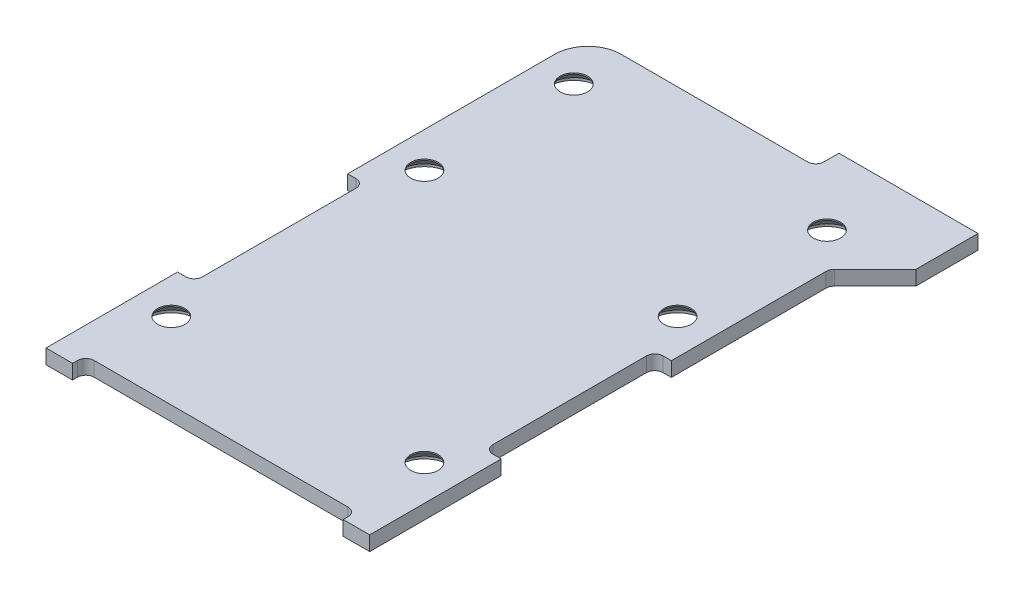
SolidWorks part; units mm, degrees
ref_plane "Front Plane" through (0, 0, 0) normal (0, 0, 1) x (1, 0, 0)
ref_plane "Top Plane" through (0, 0, 0) normal (0, 1, 0) x (1, 0, 0)
ref_plane "Right Plane" through (0, 0, 0) normal (1, 0, 0) x (0, 0, -1)
sketch "Sketch1" plane through (0, 0, 0) normal (0, 1, 0) x (1, 0, 0)
  line L1 (-18, 31.1) -> (18, 31.1)
  line L2 (-18, 31.1) -> (-18, -31.1)
  line L3 (-18, -31.1) -> (18, -31.1)
  line L4 (18, 31.1) -> (18, -31.1)
  line L5 (-18, 31.1) -> (18, -31.1) construction
  line L6 (-18, -31.1) -> (18, 31.1) construction
  point P0 (0, 0)
  dimension "D1" = 36
  dimension "D2" = 62.2
extrude "Base shape" add sketch "Sketch1" along normal blind 1.75
sketch "Sketch2" plane through (0, 1.75, 0) normal (0, 1, 0) x (1, 0, 0)
  line L0 (0, 31.1) -> (0, -31.1) construction
  line L1 (18, 31.1) -> (-18, 31.1) construction
  line L2 (-18, -31.1) -> (18, -31.1) construction
  line L4 (-18, 2.15) -> (-17.5, 2.15)
  line L5 (-18, 2.15) -> (-18, -18.35)
  line L6 (-18, -18.35) -> (-17.5, -18.35)
  line L7 (-17.5, 2.15) -> (-17.5, -18.35)
  line L8 (-17.5, -8.1) -> (-18, -8.1) construction
  line L9 (-15.25, -31.1) -> (-15.25, 31.1) construction
  line L11 (-18, -8.1) -> (18, -8.1) construction
  line L13 (15.25, 7.15) -> (15.25, -8.1) construction
  line L14 (15.25, 7.15) -> (0, 7.15) construction
  line L15 (18, -18.35) -> (17.5, -18.35)
  line L16 (17.5, 2.15) -> (17.5, -18.35)
  line L17 (18, 2.15) -> (17.5, 2.15)
  line L18 (18, 2.15) -> (18, -18.35)
  line L19 (18, -31.1) -> (18, 31.1) construction
  line L20 (-18, -31.1) -> (18, -31.1)
  line L21 (-18, -31.1) -> (-18, 14.9)
  line L22 (-18, 14.9) -> (18, 14.9)
  line L23 (18, -31.1) -> (18, 14.9)
  circle A0 centre (15.25, 7.15) radius 1.65
  circle A1 centre (15.25, -23.35) radius 1.65
  circle A2 centre (-15.25, 7.15) radius 1.65
  circle A3 centre (-15.25, -23.35) radius 1.65
  circle A4 centre (-15.25, 25.15) radius 1.65
  circle A5 centre (15.25, 25.15) radius 1.65
  line M13 (18, -31.1) -> (18, 31.1)
  line M15 (-18, 31.1) -> (-18, -31.1)
  dimension "D4" = 3.3
  dimension "D1" = 20.5
  dimension "D2" = 46
  dimension "D3" = 35
  dimension "D5" = 30.5
  dimension "D6" = 18
extrude "Cutouts" cut sketch "Sketch2" against normal up to next contours A2 | A0 | L17 L16 L15 M13 | L7 L4 L6 M15 | A3 | A1 | A4 | A5 region at (-17.75, 1.75, 8.1) region at (17.75, 1.75, 8.1) region at (15.25, 1.75, -7.15) region at (15.25, 1.75, 23.35) region at (-15.25, 1.75, -7.15) region at (-15.25, 1.75, 23.35)
sketch "Sketch3" plane through (0, 0, 0) normal (0, -1, 0) x (1, 0, 0)
  line L0 (18, -16.625) -> (19.5, -16.625) construction
  line L1 (19.5, 32.6) -> (-19.5, 32.6)
  line L2 (19.5, 32.6) -> (19.5, -32.6)
  line L3 (19.5, -32.6) -> (-19.5, -32.6)
  line L4 (-19.5, 32.6) -> (-19.5, -32.6)
  line L5 (19.5, 32.6) -> (-19.5, -32.6) construction
  line L6 (19.5, -32.6) -> (-19.5, 32.6) construction
  line L7 (0, -31.1) -> (0, -32.6) construction
  line L8 (-19.5, -31.1) -> (19.5, -31.1)
  line L9 (-19.5, -2.15) -> (19.5, -2.15)
  line L10 (-19.5, 18.35) -> (19.5, 18.35)
  line L11 (-19.5, 31.1) -> (19.5, 31.1)
  line L12 (-18, 18.35) -> (-17.5, 18.35)
  line L13 (-18, 31.1) -> (-18, 18.35)
  line L14 (18, 31.1) -> (-18, 31.1)
  line L15 (18, 18.35) -> (18, 31.1)
  line L16 (17.5, 18.35) -> (18, 18.35)
  line L17 (17.5, -2.15) -> (17.5, 18.35)
  line L18 (18, -2.15) -> (17.5, -2.15)
  line L19 (18, -31.1) -> (18, -2.15)
  line L20 (-18, -31.1) -> (18, -31.1)
  line L21 (-18, -2.15) -> (-18, -31.1)
  line L22 (-17.5, -2.15) -> (-18, -2.15)
  line L23 (-17.5, 18.35) -> (-17.5, -2.15)
  line L24 (-18, 18.35) -> (-17.5, 18.35)
  line L25 (-18, 31.1) -> (-18, 18.35)
  line L26 (18, 31.1) -> (-18, 31.1)
  line L27 (18, 18.35) -> (18, 31.1)
  line L28 (17.5, 18.35) -> (18, 18.35)
  line L29 (17.5, -2.15) -> (17.5, 18.35)
  line L30 (18, -2.15) -> (17.5, -2.15)
  line L31 (18, -31.1) -> (18, -2.15)
  line L32 (-18, -31.1) -> (18, -31.1)
  line L33 (-18, -2.15) -> (-18, -31.1)
  line L34 (-17.5, -2.15) -> (-18, -2.15)
  line L35 (-17.5, 18.35) -> (-17.5, -2.15)
  line L37 (24.7, -26.4) -> (24.7, -33.9) construction
  line L38 (7.95, -33.9) -> (24.7, -33.9) construction
  line L39 (7.95, -33.9) -> (7.95, -14.9) construction
  line L40 (24.7, -26.4) -> (19.5, -21.2) construction
  line L41 (24.7, -26.4) -> (24.7, -33.9)
  line L42 (7.95, -33.9) -> (24.7, -33.9)
  line L43 (7.95, -33.9) -> (7.95, -14.9)
  line L44 (24.7, -26.4) -> (19.5, -21.2)
  point P2 (0, 0)
  line M15 (18, -31.1) -> (18, -2.15)
  line M16 (18, 31.1) -> (-18, 31.1)
  line M17 (-18, 31.1) -> (-18, 18.35)
  line M35 (-18, -2.15) -> (-18, -31.1)
  line M36 (18, 18.35) -> (18, 31.1)
  dimension "D2" = 1.5
  dimension "D1" = 0
extrude "Extra size" add sketch "Sketch3" against normal up to surface (1.75 mm away) contours L9 L4 L8 M35 | L9 L8 L2 M15 | L11 L4 L10 M17 | L11 L10 L2 M36 | L4 L11 L2 L1 M16 | L43 L42 L41 L2 L3 | L43 L3 L2 L8 L32 region at (0, 0, 31.85) region at (18.75, 0, 24.725) region at (-18.75, 0, 24.725) region at (18.75, 0, -16.625) region at (-18.75, 0, -16.625) region at (20.0645, 0, -29.7415) region at (13.725, 0, -31.85) up to face at (15.25, 1.75, 25)
sketch "Sketch4" plane through (0, 0, 0) normal (0, 1, 0) x (1, 0, 0)
  circle A0 centre (-15.25, 25.15) radius 3
  circle A1 centre (15.25, 25.15) radius 3
  circle A2 centre (15.25, 7.15) radius 3
  circle A3 centre (-15.25, 7.15) radius 3
  circle A4 centre (-15.25, -23.35) radius 3
  circle A5 centre (15.25, -23.35) radius 3
  dimension "D1" = 6
extrude "Screw head cut" cut sketch "Sketch4" along normal blind 0.4
chamfer "Screw chamfer" distance 1.2 angle 45 6 edges at (-15.25, 0.4, 25) (15.25, 0.4, 25) (15.25, 0.4, -5.5) (15.25, 0.4, -23.5) (-15.25, 0.4, -23.5) (-15.25, 0.4, -5.5)
fillet "Front fillets" radius 4 1 edges at (-19.5, 0.875, -31.1)
sketch "Sketch6" plane through (0, 0, 32.6) normal (0, 0, 1) x (1, 0, 0)
  line L0 (19.5, 0) -> (-19.5, 0) construction
  line L1 (19.5, 1.75) -> (16.3, 1.75)
  line L2 (19.5, 1.75) -> (19.5, 0)
  line L3 (19.5, 0) -> (16.3, 0)
  line L4 (16.3, 1.75) -> (16.3, 0)
  line L7 (-19.5, 0) -> (-16.3, 0)
  line L8 (-19.5, 0) -> (-19.5, 1.75)
  line L9 (-19.5, 1.75) -> (-16.3, 1.75)
  line L10 (-16.3, 0) -> (-16.3, 1.75)
  line L11 (19.5, 1.75) -> (-19.5, 1.75) construction
  line L14 (16.3, 9.95) -> (16.3, 1.75) construction
  line L15 (-16.3, 1.75) -> (-16.3, 9.95) construction
extrude "Ledbar sides" add sketch "Sketch6" along normal up to surface (1.6 mm away)
fillet "Milling fillets" radius 1 8 edges at (-16.3, 0.875, 32.6) (16.3, 0.875, 32.6) (17.5, 0.875, -2.15) (17.5, 0.875, 18.35) (-17.5, 0.875, -2.15) (-17.5, 0.875, 18.35) (19.5, 0.875, -21.2) (7.95, 0.875, -31.1)
